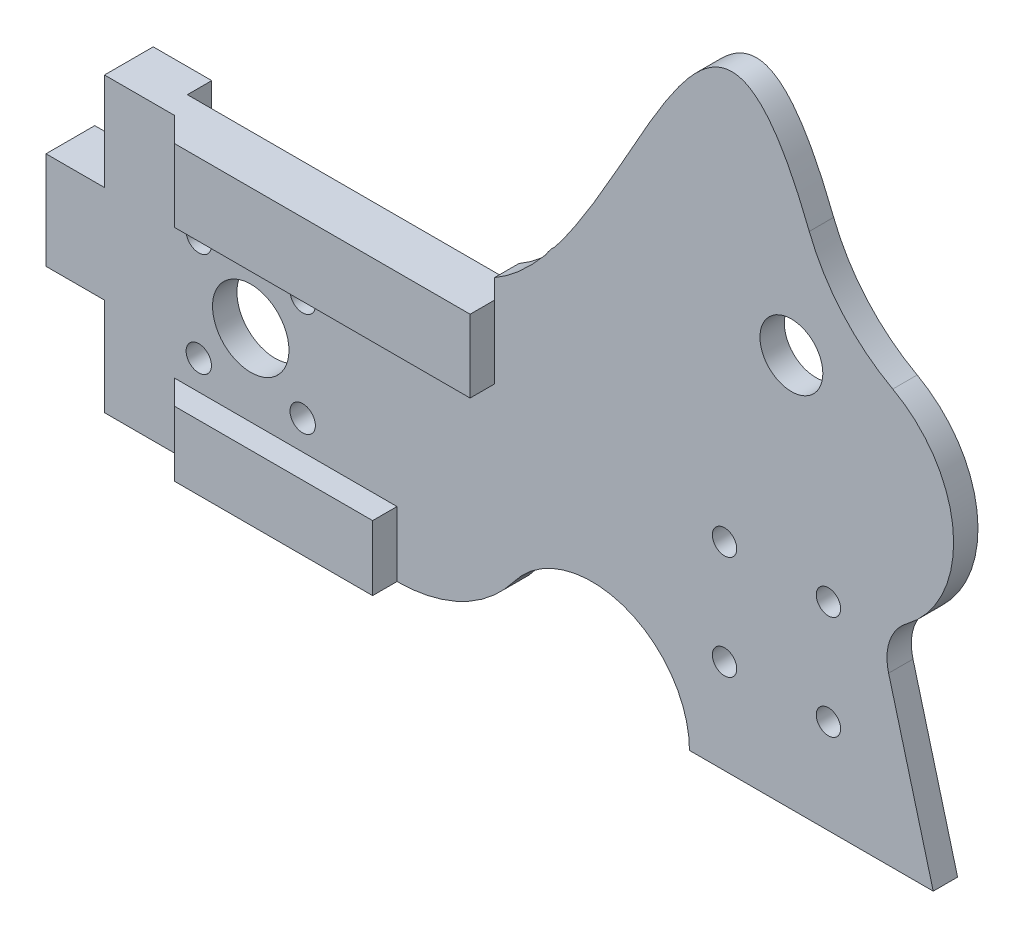
SolidWorks part; units mm, degrees
ref_plane "Front Plane" through (0, 0, 0) normal (0, 0, 1) x (1, 0, 0)
ref_plane "Top Plane" through (0, 0, 0) normal (0, 1, 0) x (1, 0, 0)
ref_plane "Right Plane" through (0, 0, 0) normal (1, 0, 0) x (0, 0, -1)
sketch "Sketch1" plane through (0, 0, 0) normal (0, 0, 1) x (1, 0, 0)
  line L0 (0, 0) -> (107.95, 0)
  line L3 (0, 38.1) -> (0, 25.4)
  line L4 (95.3675, 55.88) -> (0, 38.1)
  line L5 (0, 19.05) -> (100.2273, 19.05) construction
  line L6 (19.05, 19.05) -> (19.05, 28.62) construction
  line L7 (19.05, 19.05) -> (25.817, 25.817) construction
  line L8 (107.95, 0) -> (100.9363, 26.1756)
  line L10 (0, 12.7) -> (0, 0)
  line L11 (0, 25.4) -> (-7.62, 25.4)
  line L13 (0, 12.7) -> (-7.62, 12.7)
  line L14 (-7.62, 25.4) -> (-7.62, 12.7)
  line L15 (100.9363, 26.1756) -> (100.8688, 26.4276)
  arc A0 (100.8688, 26.4276) -> (95.3675, 55.88) centre (95.3675, 40.64) ccw
  circle A1 centre (95.3675, 40.64) radius 4.0957 construction
  circle A2 centre (19.05, 19.05) radius 9.57 construction
  circle A3 centre (25.817, 25.817) radius 1.651
  circle A4 centre (25.817, 12.283) radius 1.651
  circle A5 centre (12.283, 12.283) radius 1.651
  circle A6 centre (12.283, 25.817) radius 1.651
  point P16 (0, 0)
  point P26 (19.05, 19.05)
  dimension "D1" = 8.1915
  dimension "D5" = 15.24
  dimension "D4" = 19.14
  dimension "D7" = 3.302
  dimension "D11" = 97.0107
  dimension "D2" = 38.1
  dimension "D3" = 40.64
  dimension "D6" = 107.95
  dimension "D8" = 45
  dimension "D9" = 4
  dimension "D10" = 19.05
  dimension "D12" = 75
  dimension "D14" = 12.7
  dimension "D15" = 12.7
  dimension "D16" = 7.62
extrude "Boss-Extrude1" add sketch "Sketch1" along normal blind 3.175
sketch "Sketch2" plane through (0, 0, 3.175) normal (0, 0, 1) x (1, 0, 0)
  circle A0 centre (95.3675, 40.64) radius 38.1 construction
sketch "Sketch6" plane through (0, 0, 3.175) normal (0, 0, 1) x (1, 0, 0)
  line L0 (0, 0) -> (107.95, 0) construction
  line L1 (50.8, 0) -> (76.2, 0)
  arc A0 (76.2, 0) -> (50.8, 0) centre (63.5, 0) ccw
  dimension "D1" = 25.4
  dimension "D2" = 31.75
extrude "Cut-Extrude2" cut sketch "Sketch6" against normal blind 6.35
sketch "Sketch7" plane through (0, 0, 3.175) normal (0, 0, 1) x (1, 0, 0)
  line L0 (12.283, 25.817) -> (25.817, 12.283) construction
  line L1 (12.283, 12.283) -> (25.817, 25.817) construction
  line L2 (12.283, 25.817) -> (78.4839, 25.817) construction
  line L3 (11.7326, 12.283) -> (12.283, 12.283) construction
  circle A0 centre (19.05, 19.05) radius 4.9784
  circle A4 centre (80.7666, 12.283) radius 1.5875
  circle A5 centre (94.2997, 12.283) radius 1.5875
  circle A6 centre (80.7666, 25.817) radius 1.5875
  circle A7 centre (94.2997, 25.817) radius 1.5875
  dimension "D1" = 9.9568
  dimension "D2" = 3.175
  dimension "D3" = 13.5331
extrude "Cut-Extrude3" cut sketch "Sketch7" against normal through all
fillet "Fillet1" radius 6.35 1 edges at (100.8688, 26.4276, 1.5875)
sketch "Sketch8" plane through (0, 0, 3.175) normal (0, 0, 1) x (1, 0, 0)
  line L1 (0, 38.1) -> (50.8, 38.1)
  line L2 (0, 38.1) -> (0, 50.8)
  line L3 (0, 50.8) -> (50.8, 50.8)
  line L4 (50.8, 38.1) -> (50.8, 50.8)
  dimension "D1" = 50.8
  dimension "D2" = 12.7
extrude "Cut-Extrude4" cut sketch "Sketch8" against normal blind 50.8
sketch "Sketch9" plane through (0, 0, 3.175) normal (0, 0, 1) x (1, 0, 0)
  line L3 (50.8, 40.64) -> (57.15, 40.64)
  line L5 (57.15, 40.64) -> (50.8, 40.64)
  line L6 (57.15, 40.64) -> (57.15, 50.8)
  line L7 (57.15, 50.8) -> (50.8, 50.8)
  line L8 (50.8, 40.64) -> (50.8, 50.8)
  line L9 (0, 38.1) -> (50.8, 38.1) construction
  line M8 (50.8, 47.571) -> (50.8, 38.1)
  line M21 (95.3675, 55.88) -> (50.8, 47.571)
  dimension "D1" = 10.16
  dimension "D2" = 2.54
  dimension "D3" = 6.35
extrude "Cut-Extrude5" cut sketch "Sketch9" against normal blind 19.304 contours L3 L6 M21 M8 region at (54.0583, 44.4092, 3.175)
fillet "Fillet6" radius 6.35 1 edges at (57.15, 40.64, 1.5875)
fillet "Fillet7" radius 6.35 1 edges at (57.15, 48.7549, 1.5875)
fillet "Fillet8" radius 19.05 1 edges at (50.8, 0, 1.5875)
sketch "Sketch12" plane through (0, 0, 3.175) normal (0, 0, 1) x (1, 0, 0)
  line L0 (107.95, 0) -> (146.812, 0) construction
  line L1 (8.0257, 45.4128) -> (80.6683, 75.7903) construction
  line L2 (95.3675, 40.64) -> (80.6683, 75.7903) construction
  line L3 (80.6683, 75.7903) -> (79.4434, 78.7195) construction
  line L4 (50.8, 40.64) -> (85.0271, 40.64)
  line L5 (85.0271, 40.64) -> (95.3675, 55.88)
  arc A0 (61.8128, 49.6242) -> (56.8883, 45.1859) centre (62.9766, 43.3817) ccw construction
  circle A1 centre (19.05, 19.05) radius 28.575 construction
  circle A2 centre (95.3675, 40.64) radius 38.1 construction
  circle A3 centre (80.6683, 75.7903) radius 3.175 construction
  spline S0 degree 3 poles (50.8, 40.64) (70.7778, 52.1788) (78.5943, 111.5434) (95.3675, 55.88) knots 0 0 0 0 1 1 1 1
  dimension "D2" = 6.35
  dimension "D1" = 38.862
extrude "Boss-Extrude2" add sketch "Sketch12" against normal blind 3.175
fillet "Fillet9" radius 24.13 1 edges at (95.3675, 55.88, 1.5875)
sketch "Sketch13" plane through (0, 0, 0) normal (0, 0, -1) x (-1, 0, 0)
  line L1 (-50.8, 38.1) -> (-9.1321, 38.1)
  line L2 (-50.8, 38.1) -> (-50.8, 28.6404)
  line L3 (-50.8, 28.6404) -> (-9.1321, 28.6404)
  line L6 (-9.1321, 8.4682) -> (-38.1, 8.4682)
  line L7 (-9.1321, 8.4682) -> (-9.1321, 0)
  line L8 (-9.1321, 0) -> (-38.1, 0)
  line L9 (-38.1, 8.4682) -> (-38.1, 0)
  line L10 (-9.1321, 38.1) -> (-9.1321, 28.6404)
extrude "Boss-Extrude3" add sketch "Sketch13" against normal blind 6.35
sketch "Sketch16" plane through (0, 0, 3.175) normal (0, 0, 1) x (1, 0, 0)
  circle A0 centre (89.4737, 51.217) radius 4.0958
  circle A1 centre (94.2997, 25.817) radius 1.5875 construction
  dimension "D1" = 25.4
  dimension "D2" = 4.826
extrude "Cut-Extrude8" cut sketch "Sketch16" against normal through all
sketch "Sketch18" plane through (0, 0, 3.175) normal (0, 0, 1) x (1, 0, 0)
  line L0 (0, 0) -> (7.62, 0)
  line L1 (0, 0) -> (9.1321, 0) construction
  line L2 (7.62, 0) -> (7.62, 38.1)
  line L3 (0, 38.1) -> (9.1321, 38.1) construction
  line L4 (7.62, 38.1) -> (0, 38.1)
  line L5 (0, 38.1) -> (0, 25.4)
  line L6 (0, 25.4) -> (-7.62, 25.4)
  line L7 (-7.62, 25.4) -> (-7.62, 12.7)
  line L8 (-7.62, 12.7) -> (0, 12.7)
  line L9 (0, 12.7) -> (0, 0)
  dimension "D1" = 7.62
extrude "Boss-Extrude4" add sketch "Sketch18" against normal blind 6.35
sketch "Sketch19" plane through (0, 38.1, 0) normal (0, 1, 0) x (1, 0, 0)
  line L0 (9.1321, -3.175) -> (12.3071, -6.35)
  line L1 (9.1321, -6.35) -> (9.1321, -3.175) construction
  line L2 (0, -3.175) -> (9.1321, -3.175) construction
  line L3 (9.1321, -6.35) -> (50.8, -6.35) construction
  line L4 (12.3071, -6.35) -> (9.1321, -6.35)
  line L5 (9.1321, -6.35) -> (9.1321, -3.175)
  dimension "D1" = 45
extrude "Cut-Extrude9" cut sketch "Sketch19" against normal through all
